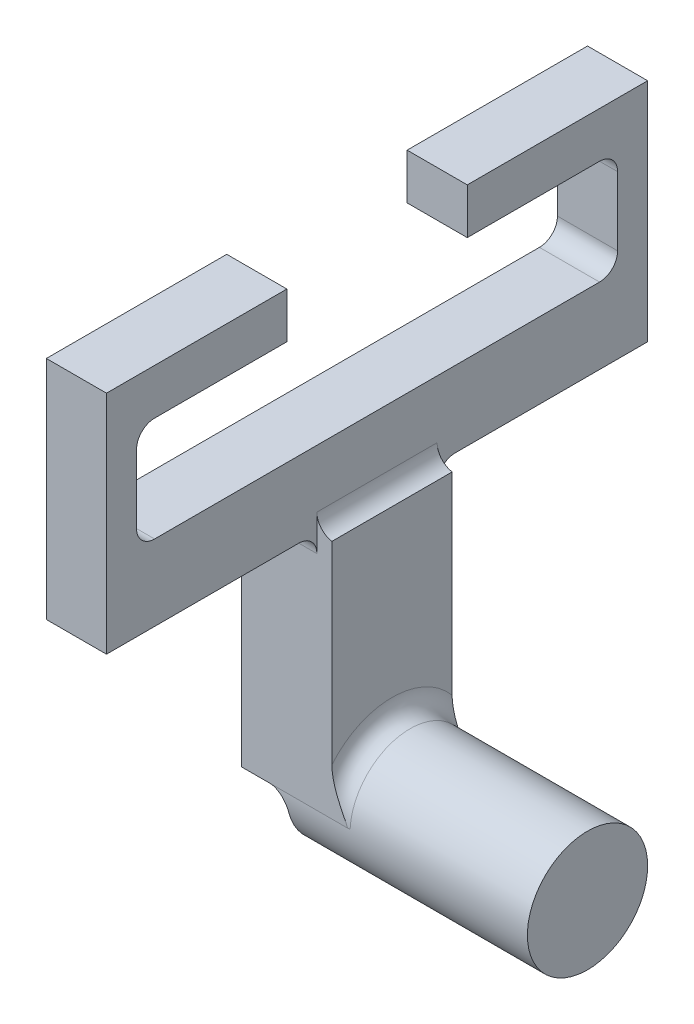
SolidWorks part; units mm, degrees
material "6061-T6 (SS)"
ref_plane "Front Plane" through (0, 0, 0) normal (0, 0, 1) x (1, 0, 0)
ref_plane "Top Plane" through (0, 0, 0) normal (0, 1, 0) x (1, 0, 0)
ref_plane "Right Plane" through (0, 0, 0) normal (1, 0, 0) x (0, 0, -1)
sketch "Sketch2" plane through (0, 0, 0) normal (1, 0, 0) x (0, 0, -1)
  circle A0 centre (0, 0) radius 12.7
  dimension "D1" = 25.4
extrude "Boss-Extrude1" add sketch "Sketch2" along normal blind 50.8 contours A0
sketch "Sketch3" plane through (0, 0, 0) normal (-1, 0, 0) x (0, 0, 1)
  line L1 (-12.6854, 0.6087) -> (12.7146, 0.6087)
  line L2 (-12.6854, 0.6087) -> (-12.6854, 51.4087)
  line L3 (-12.6854, 51.4087) -> (12.7146, 51.4087)
  line L4 (12.7146, 0.6087) -> (12.7146, 51.4087)
  circle A0 centre (0, 0) radius 12.7 construction
  dimension "D1" = 25.4
  dimension "D2" = 50.8
extrude "Boss-Extrude2" add sketch "Sketch3" against normal mid plane 19.05
sketch "Sketch5" plane through (0, 0, 0) normal (1, 0, 0) x (0, 0, -1)
  line L1 (50.8, 67.3933) -> (-50.8, 67.3933)
  line L2 (50.8, 67.3933) -> (50.8, 51.3913)
  line L3 (50.8, 51.3913) -> (-50.8, 51.3913)
  line L4 (-50.8, 67.3933) -> (-50.8, 51.3913)
  line L5 (50.8, 67.3933) -> (-50.8, 51.3913) construction
  line L6 (50.8, 51.3913) -> (-50.8, 67.3933) construction
  point P0 (0, 59.3923)
  dimension "D1" = 101.6
  dimension "D2" = 16.002
extrude "Boss-Extrude3" add sketch "Sketch5" along normal mid plane 12.7 separate body
sketch "Sketch6" plane through (0, 0, 0) normal (1, 0, 0) x (0, 0, -1)
  line L1 (-50.8, 51.3913) -> (-57.15, 51.3913)
  line L2 (-50.8, 51.3913) -> (-50.8, 89.4913)
  line L3 (-50.8, 89.4913) -> (-57.15, 89.4913)
  line L4 (-57.15, 51.3913) -> (-57.15, 89.4913)
  line L5 (50.8, 51.3913) -> (57.15, 51.3913)
  line L6 (50.8, 51.3913) -> (50.8, 89.4913)
  line L7 (50.8, 89.4913) -> (57.15, 89.4913)
  line L8 (57.15, 51.3913) -> (57.15, 89.4913)
  dimension "D1" = 6.35
  dimension "D2" = 38.1
  dimension "D3" = 6.35
  dimension "D4" = 38.1
extrude "Boss-Extrude4" add sketch "Sketch6" along normal mid plane 12.7
sketch "Sketch7" plane through (0, 0, 0) normal (1, 0, 0) x (0, 0, -1)
  line L1 (-57.15, 89.4913) -> (-19.05, 89.4913)
  line L2 (-57.15, 89.4913) -> (-57.15, 99.1433)
  line L3 (-57.15, 99.1433) -> (-19.05, 99.1433)
  line L4 (-19.05, 89.4913) -> (-19.05, 99.1433)
  line L5 (57.15, 89.4913) -> (19.05, 89.4913)
  line L6 (57.15, 89.4913) -> (57.15, 99.1433)
  line L7 (57.15, 99.1433) -> (19.05, 99.1433)
  line L8 (19.05, 89.4913) -> (19.05, 99.1433)
  dimension "D1" = 38.1
  dimension "D2" = 38.1
  dimension "D3" = 9.652
  dimension "D4" = 9.652
extrude "Boss-Extrude5" add sketch "Sketch7" along normal mid plane 12.7
combine bodies "Combine1" operation type add bodies to combine 102 105
fillet "Fillet1" radius 3.81 7 edges at (0, 51.3913, 12.7146) (0, 51.3913, -12.6854) (9.525, 12.7, 0) (0, 89.4913, -50.8) (0, 67.3933, -50.8) (0, 89.4913, 50.8) (0, 67.3933, 50.8)
fillet "Fillet2" radius 3.81 3 edges at (0, 0.6087, 0) (-6.35, 51.4087, 0.0146) (6.35, 51.4087, 0.0146)
equation "\"d_A\"= 1.00in"
equation "\"t_B\"= 0.50in"
equation "\"h_B\"= 2.00in"
equation "\"h_C\"= 0.625in"
equation "\"L_C\"= 4.00in"
equation "\"L_D\"= 1.500in"
equation "\"h_E\"= 0.375in"
equation "\"L_E\"= 1.500in"
equation "\"W_B\"= \"d_A\""
equation "\"L_A\"= 2.00in"
equation "\"t_C\"= \"t_B\""
equation "\"t_D\"= \"t_B\""
equation "\"t_E\"= \"t_B\""
